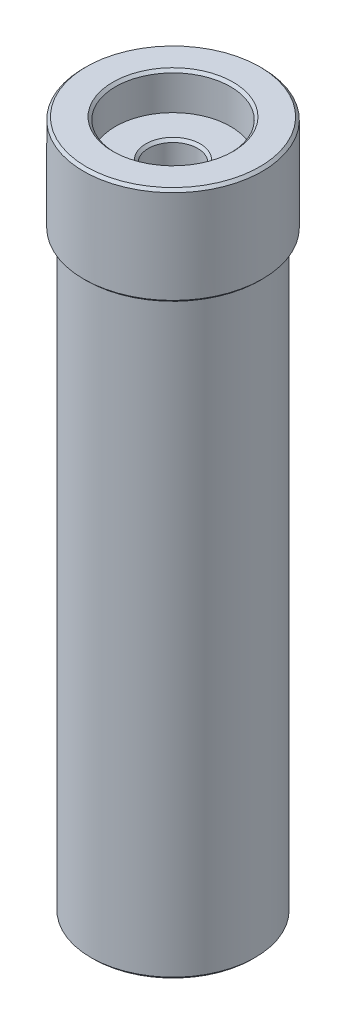
SolidWorks part; units mm, degrees
ref_plane "Front Plane" through (0, 0, 0) normal (0, 0, 1) x (1, 0, 0)
ref_plane "Top Plane" through (0, 0, 0) normal (0, 1, 0) x (1, 0, 0)
ref_plane "Right Plane" through (0, 0, 0) normal (1, 0, 0) x (0, 0, -1)
sketch "Sketch1" plane through (0, 0, 0) normal (0, 1, 0) x (1, 0, 0)
  circle A0 centre (0, 0) radius 15.875
  dimension "D1" = 31.75
extrude "Boss-Extrude1" add sketch "Sketch1" along normal blind 114.3
sketch "Sketch2" plane through (0, 114.3, 0) normal (0, 1, 0) x (1, 0, 0)
  circle A0 centre (0, 0) radius 17.272
  dimension "D1" = 34.544
extrude "Boss-Extrude2" add sketch "Sketch2" along normal blind 19.05
hole_wizard "1-12 Tapped Hole2" positions "Sketch3" profile "Sketch5" tap size "1-12" standard "ANSI Inch"
sketch "Sketch3" plane through (0, 0, 0) normal (0, -1, 0) x (-1, 0, 0)
  point P0 (0, 0)
sketch "Sketch5" plane through (0, 0, 0) normal (1, 0, 0) x (0, 0, -1)
  line L0 (0, 0) -> (0, 118.795)
  line L1 (0, 118.795) -> (11.7081, 111.76)
  line L2 (11.7081, 111.76) -> (11.7081, 0)
  line L5 (11.7081, 0) -> (0, 0)
  line L10 (0, 118.795) -> (-11.7081, 111.76) construction
  line L11 (0, -6.35) -> (0, 107.95) construction
  dimension "Tap Drill Dia." = 23.4163
  dimension "Tap Drill Depth" = 111.76
  dimension "Drill Angle" = 118
cosmetic thread "Hole Thread3" parameters "D1"=50.8, "D2"=25.4
sketch "Sketch10" plane through (0, 133.35, 0) normal (0, 1, 0) x (1, 0, 0)
  circle A0 centre (0, 0) radius 11.1125
  dimension "D1" = 22.225
extrude "Cut-Extrude1" cut sketch "Sketch10" against normal blind 7.1628
hole_wizard "3/8 (0.375) Diameter Hole1" positions "Sketch11" profile "Sketch12" hole size "3/8" standard "ANSI Inch" end condition through all
sketch "Sketch11" plane through (0, 126.1872, 0) normal (0, 1, 0) x (1, 0, 0)
  point P1 (0, 0)
sketch "Sketch12" plane through (0, 126.1872, 0) normal (1, 0, 0) x (0, 0, 1)
  line L0 (0, 0) -> (0, 126.1872)
  line L1 (0, 126.1872) -> (4.7625, 126.1872)
  line L2 (4.7625, 126.1872) -> (4.7625, 0)
  line L5 (4.7625, 0) -> (0, 0)
  line L11 (0, -6.35) -> (0, 107.95) construction
  dimension "Thru Hole Dia." = 9.525
  dimension "Thru Hole Depth" = 126.1872
chamfer "Chamfer2" distance 0.508 angle 45 5 edges at (0, 0, 15.875) (0, 114.3, 17.272) (0, 133.35, 17.272) (0, 126.1872, 4.7625) (0, 133.35, 11.1125)
